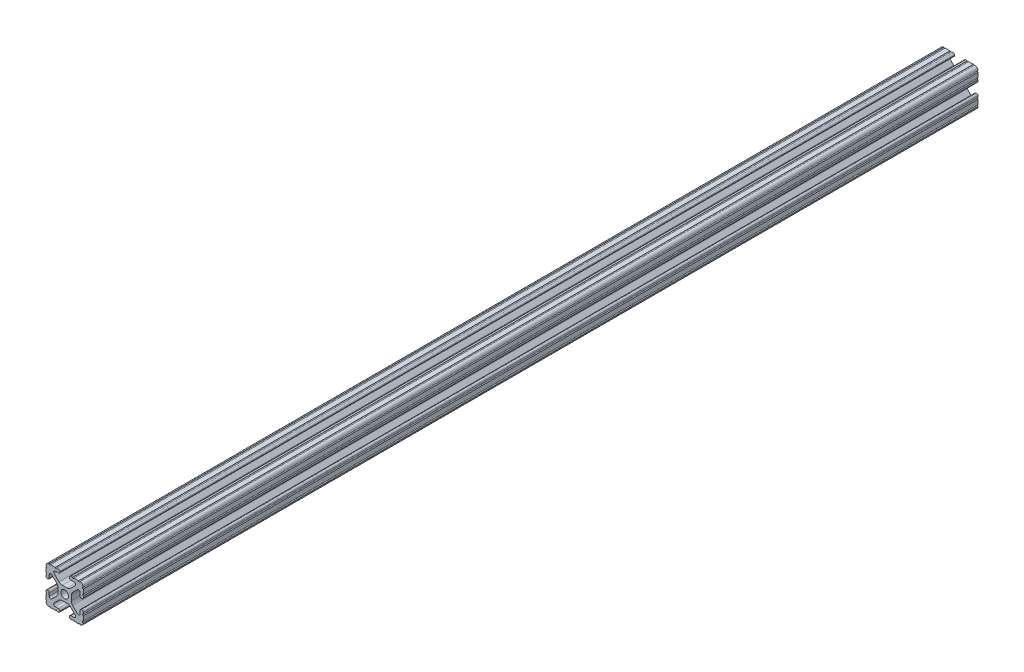
SolidWorks part; units mm, degrees
ref_plane "Front Plane" through (0, 0, 0) normal (0, 0, 1) x (1, 0, 0)
ref_plane "Top Plane" through (0, 0, 0) normal (0, 1, 0) x (1, 0, 0)
ref_plane "Right Plane" through (0, 0, 0) normal (1, 0, 0) x (0, 0, -1)
sketch "Sketch1" plane through (0, 0, 0) normal (0, 0, 1) x (1, 0, 0)
  line L88 (-7.1797, -8.6452) -> (-3.9523, -5.4237)
  line L89 (-1.7093, -4.4958) -> (1.7093, -4.4958)
  line L90 (3.9523, -5.4237) -> (7.1797, -8.6452)
  line L91 (6.4164, -10.4902) -> (4.2875, -10.4902)
  line L92 (3.2385, -11.5392) -> (3.2385, -11.651)
  line L93 (4.2875, -12.7) -> (5.3171, -12.7)
  line L94 (6.3331, -12.7) -> (9.5504, -12.7)
  line L95 (12.7, -9.5504) -> (12.7, -6.3331)
  line L96 (12.7, -5.3171) -> (12.7, -4.2875)
  line L97 (11.651, -3.2385) -> (11.5392, -3.2385)
  line L98 (10.4902, -4.2875) -> (10.4902, -6.4021)
  line L99 (8.7371, -7.1294) -> (5.441, -3.8408)
  line L100 (4.5085, -1.5932) -> (4.5085, 1.5932)
  line L101 (5.441, 3.8408) -> (8.7371, 7.1294)
  line L102 (10.4902, 6.4021) -> (10.4902, 4.2875)
  line L103 (11.5392, 3.2385) -> (11.651, 3.2385)
  line L104 (12.7, 4.2875) -> (12.7, 5.3171)
  line L105 (12.7, 6.3331) -> (12.7, 9.5504)
  line L106 (9.5504, 12.7) -> (6.3331, 12.7)
  line L107 (5.3171, 12.7) -> (4.2875, 12.7)
  line L108 (3.2385, 11.651) -> (3.2385, 11.5392)
  line L109 (4.2875, 10.4902) -> (6.4768, 10.4902)
  line L110 (7.207, 8.7244) -> (3.8983, 5.4232)
  line L111 (1.6558, 4.4958) -> (-1.6558, 4.4958)
  line L112 (-3.8983, 5.4232) -> (-7.207, 8.7244)
  line L113 (-6.4768, 10.4902) -> (-4.2875, 10.4902)
  line L114 (-3.2385, 11.5392) -> (-3.2385, 11.651)
  line L115 (-4.2875, 12.7) -> (-5.3171, 12.7)
  line L116 (-6.3331, 12.7) -> (-9.5504, 12.7)
  line L117 (-12.7, 9.5504) -> (-12.7, 6.3331)
  line L118 (-12.7, 5.3171) -> (-12.7, 4.2875)
  line L119 (-11.651, 3.2385) -> (-11.5392, 3.2385)
  line L120 (-10.4902, 4.2875) -> (-10.4902, 6.4021)
  line L121 (-8.7371, 7.1294) -> (-5.441, 3.8408)
  line L122 (-4.5085, 1.5932) -> (-4.5085, -1.5932)
  line L123 (-5.441, -3.8408) -> (-8.7371, -7.1294)
  line L124 (-10.4902, -6.4021) -> (-10.4902, -4.2875)
  line L125 (-11.5392, -3.2385) -> (-11.651, -3.2385)
  line L126 (-12.7, -4.2875) -> (-12.7, -5.3171)
  line L127 (-12.7, -6.3331) -> (-12.7, -9.5504)
  line L128 (-9.5504, -12.7) -> (-6.3331, -12.7)
  line L129 (-5.3171, -12.7) -> (-4.2875, -12.7)
  line L130 (-3.2385, -11.651) -> (-3.2385, -11.5392)
  line L131 (-4.2875, -10.4902) -> (-6.4164, -10.4902)
  circle A1 centre (0, 0) radius 2.6035
  arc A104 (-7.1797, -8.6452) -> (-6.4164, -10.4902) centre (-6.4164, -9.4098) ccw
  arc A105 (-1.7093, -4.4958) -> (-3.9523, -5.4237) centre (-1.7093, -7.6708) ccw
  arc A106 (3.9523, -5.4237) -> (1.7093, -4.4958) centre (1.7093, -7.6708) ccw
  arc A107 (6.4164, -10.4902) -> (7.1797, -8.6452) centre (6.4164, -9.4098) ccw
  arc A108 (4.2875, -10.4902) -> (3.2385, -11.5392) centre (4.2875, -11.5392) ccw
  arc A109 (3.2385, -11.651) -> (4.2875, -12.7) centre (4.2875, -11.651) ccw
  arc A110 (6.3331, -12.7) -> (5.3171, -12.7) centre (5.8251, -12.7) ccw
  arc A111 (10.5664, -12.6998) -> (9.5504, -12.7) centre (10.0584, -12.7) ccw
  arc A112 (10.5664, -12.6998) -> (12.6998, -10.5664) centre (10.5918, -10.5918) ccw
  arc A113 (12.7, -9.5504) -> (12.6998, -10.5664) centre (12.7, -10.0584) ccw
  arc A114 (12.7, -5.3171) -> (12.7, -6.3331) centre (12.7, -5.8251) ccw
  arc A115 (12.7, -4.2875) -> (11.651, -3.2385) centre (11.651, -4.2875) ccw
  arc A116 (11.5392, -3.2385) -> (10.4902, -4.2875) centre (11.5392, -4.2875) ccw
  arc A117 (8.7371, -7.1294) -> (10.4902, -6.4021) centre (9.4628, -6.4021) ccw
  arc A118 (4.5085, -1.5932) -> (5.441, -3.8408) centre (7.6835, -1.5932) ccw
  arc A119 (5.441, 3.8408) -> (4.5085, 1.5932) centre (7.6835, 1.5932) ccw
  arc A120 (10.4902, 6.4021) -> (8.7371, 7.1294) centre (9.4628, 6.4021) ccw
  arc A121 (10.4902, 4.2875) -> (11.5392, 3.2385) centre (11.5392, 4.2875) ccw
  arc A122 (11.651, 3.2385) -> (12.7, 4.2875) centre (11.651, 4.2875) ccw
  arc A123 (12.7, 6.3331) -> (12.7, 5.3171) centre (12.7, 5.8251) ccw
  arc A124 (12.6998, 10.5664) -> (12.7, 9.5504) centre (12.7, 10.0584) ccw
  arc A125 (12.6998, 10.5664) -> (10.5664, 12.6998) centre (10.5918, 10.5918) ccw
  arc A126 (9.5504, 12.7) -> (10.5664, 12.6998) centre (10.0584, 12.7) ccw
  arc A127 (5.3171, 12.7) -> (6.3331, 12.7) centre (5.8251, 12.7) ccw
  arc A128 (4.2875, 12.7) -> (3.2385, 11.651) centre (4.2875, 11.651) ccw
  arc A129 (3.2385, 11.5392) -> (4.2875, 10.4902) centre (4.2875, 11.5392) ccw
  arc A130 (7.207, 8.7244) -> (6.4768, 10.4902) centre (6.4768, 9.4563) ccw
  arc A131 (1.6558, 4.4958) -> (3.8983, 5.4232) centre (1.6558, 7.6708) ccw
  arc A132 (-3.8983, 5.4232) -> (-1.6558, 4.4958) centre (-1.6558, 7.6708) ccw
  arc A133 (-6.4768, 10.4902) -> (-7.207, 8.7244) centre (-6.4768, 9.4563) ccw
  arc A134 (-4.2875, 10.4902) -> (-3.2385, 11.5392) centre (-4.2875, 11.5392) ccw
  arc A135 (-3.2385, 11.651) -> (-4.2875, 12.7) centre (-4.2875, 11.651) ccw
  arc A136 (-6.3331, 12.7) -> (-5.3171, 12.7) centre (-5.8251, 12.7) ccw
  arc A137 (-10.5664, 12.6998) -> (-9.5504, 12.7) centre (-10.0584, 12.7) ccw
  arc A138 (-10.5664, 12.6998) -> (-12.6998, 10.5664) centre (-10.5918, 10.5918) ccw
  arc A139 (-12.7, 9.5504) -> (-12.6998, 10.5664) centre (-12.7, 10.0584) ccw
  arc A140 (-12.7, 5.3171) -> (-12.7, 6.3331) centre (-12.7, 5.8251) ccw
  arc A141 (-12.7, 4.2875) -> (-11.651, 3.2385) centre (-11.651, 4.2875) ccw
  arc A142 (-11.5392, 3.2385) -> (-10.4902, 4.2875) centre (-11.5392, 4.2875) ccw
  arc A143 (-8.7371, 7.1294) -> (-10.4902, 6.4021) centre (-9.4628, 6.4021) ccw
  arc A144 (-4.5085, 1.5932) -> (-5.441, 3.8408) centre (-7.6835, 1.5932) ccw
  arc A145 (-5.441, -3.8408) -> (-4.5085, -1.5932) centre (-7.6835, -1.5932) ccw
  arc A146 (-10.4902, -6.4021) -> (-8.7371, -7.1294) centre (-9.4628, -6.4021) ccw
  arc A147 (-10.4902, -4.2875) -> (-11.5392, -3.2385) centre (-11.5392, -4.2875) ccw
  arc A148 (-11.651, -3.2385) -> (-12.7, -4.2875) centre (-11.651, -4.2875) ccw
  arc A149 (-12.7, -6.3331) -> (-12.7, -5.3171) centre (-12.7, -5.8251) ccw
  arc A150 (-12.6998, -10.5664) -> (-12.7, -9.5504) centre (-12.7, -10.0584) ccw
  arc A151 (-12.6998, -10.5664) -> (-10.5664, -12.6998) centre (-10.5918, -10.5918) ccw
  arc A152 (-9.5504, -12.7) -> (-10.5664, -12.6998) centre (-10.0584, -12.7) ccw
  arc A153 (-5.3171, -12.7) -> (-6.3331, -12.7) centre (-5.8251, -12.7) ccw
  arc A154 (-4.2875, -12.7) -> (-3.2385, -11.651) centre (-4.2875, -11.651) ccw
  arc A155 (-3.2385, -11.5392) -> (-4.2875, -10.4902) centre (-4.2875, -11.5392) ccw
extrude "Boss-Extrude1" add sketch "Sketch1" along normal mid plane 609.6
sketch "Sketch2" plane through (12.7, 0, 0) normal (1, 0, 0) x (0, 0, -1)
  line L0 (-56.5865, 13.6438) -> (-56.5865, -14.2345) construction
  line L1 (-56.5865, -14.2345) -> (310.7431, -14.2345)
  line L2 (310.7431, -14.2345) -> (310.7431, 13.6438)
  line L3 (310.7431, 13.6438) -> (-56.5865, 13.6438)
  line L4 (-56.5865, 13.6438) -> (496.7153, 13.6438)
  line L5 (496.7153, 12.7) -> (496.7153, 19.05) construction
  line L6 (-56.5865, -14.2345) -> (496.7153, -14.2345)
  line L7 (496.7153, -14.2345) -> (496.7153, 13.6438)
  line L9 (-305.4758, 13.3523) -> (-289.2182, 13.3523)
  line L10 (-305.4758, 13.3523) -> (-305.4758, -14.2345)
  line L11 (-305.4758, -14.2345) -> (-289.2182, -14.2345)
  line L12 (-289.2182, 13.3523) -> (-289.2182, -14.2345)
extrude "Cut-Extrude1" cut sketch "Sketch2" against normal blind 26.162 and the other way blind 1.778 rebuild error yes
